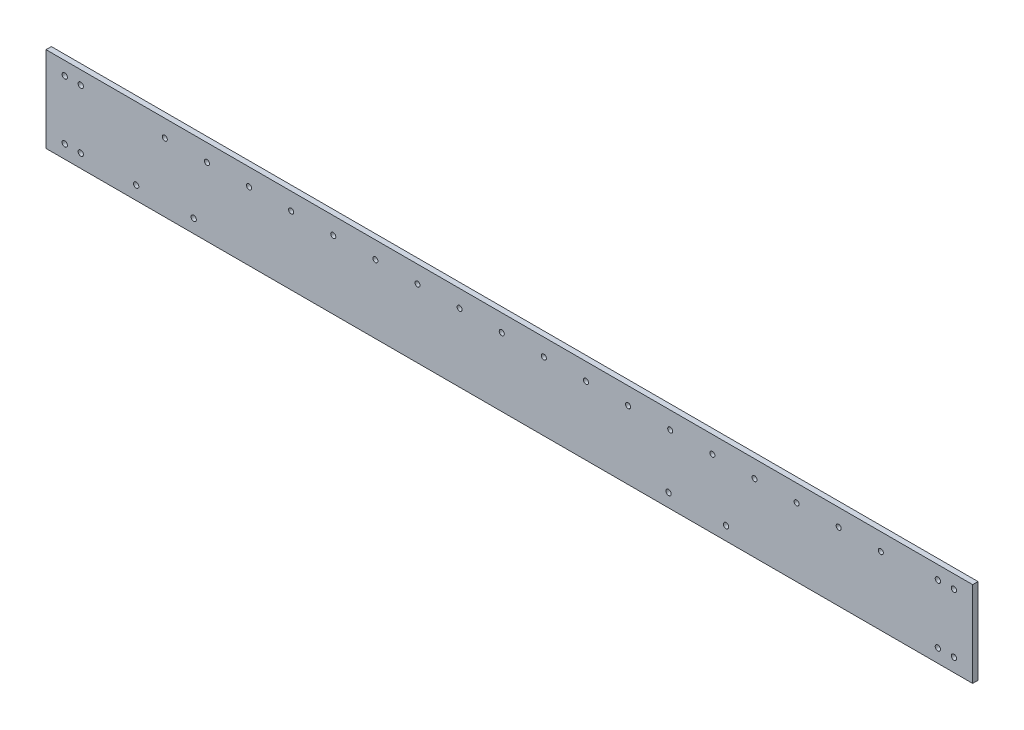
SolidWorks part; units mm, degrees
ref_plane "Front Plane" through (0, 0, 0) normal (0, 0, 1) x (1, 0, 0)
ref_plane "Top Plane" through (0, 0, 0) normal (0, 1, 0) x (1, 0, 0)
ref_plane "Right Plane" through (0, 0, 0) normal (1, 0, 0) x (0, 0, -1)
sketch "Sketch1" plane through (0, 0, 0) normal (1, 0, 0) x (0, 0, -1)
  line L0 (0, 0) -> (-3.175, 0)
  line L3 (-3.175, 0) -> (-3.175, 50.8)
  line L4 (-3.175, 50.8) -> (0, 50.8)
  line L5 (0, 50.8) -> (0, 0)
  dimension "LHeight" = 50.8
  dimension "LMaterialThickness" = 3.175
extrude "Boss-Extrude1" add sketch "Sketch1" along normal blind 550
sketch "LeftSideHoles-Sketch4" plane through (0, 0, 3.175) normal (0, 0, 1) x (1, 0, 0)
  line L0 (550, 50.8) -> (550, 0) construction
  line L1 (0, 50.8) -> (0, 0) construction
  line L2 (550, 50.8) -> (550, 0) construction
  line L3 (550, 50.8) -> (0, 50.8) construction
  line L4 (550, 0) -> (0, 0) construction
  line L5 (550, 50.8) -> (0, 50.8) construction
  line L6 (0, 50.8) -> (0, 0) construction
  circle A1 centre (11.1125, 42.8625) radius 1.5875
  circle A3 centre (529.3625, 42.8625) radius 1.5875
  circle A4 centre (20.6375, 42.8625) radius 1.5875
  circle A5 centre (538.8875, 42.8625) radius 1.5875
  circle A6 centre (11.1125, 7.9375) radius 1.5875
  circle A7 centre (20.6375, 7.9375) radius 1.5875
  circle A8 centre (529.3625, 7.9375) radius 1.5875
  circle A9 centre (538.8875, 7.9375) radius 1.5875
  circle A10 centre (495.5, 40.575) radius 1.5
  circle A11 centre (470.5, 40.575) radius 1.5
  circle A12 centre (445.5, 40.575) radius 1.5
  circle A13 centre (420.5, 40.575) radius 1.5
  circle A14 centre (395.5, 40.575) radius 1.5
  circle A15 centre (370.5, 40.575) radius 1.5
  circle A16 centre (345.5, 40.575) radius 1.5
  circle A17 centre (320.5, 40.575) radius 1.5
  circle A18 centre (295.5, 40.575) radius 1.5
  circle A19 centre (270.5, 40.575) radius 1.5
  circle A20 centre (245.5, 40.575) radius 1.5
  circle A21 centre (220.5, 40.575) radius 1.5
  circle A22 centre (195.5, 40.575) radius 1.5
  circle A23 centre (170.5, 40.575) radius 1.5
  circle A24 centre (145.5, 40.575) radius 1.5
  circle A25 centre (120.5, 40.575) radius 1.5
  circle A26 centre (95.5, 40.575) radius 1.5
  circle A27 centre (70.5, 40.575) radius 1.5
  circle A28 centre (53.5125, 7.9375) radius 1.5875
  circle A31 centre (369.5125, 7.9375) radius 1.5875
  circle A33 centre (87.6375, 7.9375) radius 1.5875
  circle A35 centre (403.6375, 7.9375) radius 1.5875
  dimension "D2" = 3.175
  dimension "D10" = 3
  dimension "D14" = 3.175
  dimension "D4" = 7.9375
  dimension "D1" = 11.1125
  dimension "D6" = 20.6375
  dimension "D3" = 11.1125
  dimension "D5" = 20.6375
  dimension "D7" = 7.9375
  dimension "D8" = 54.5
  dimension "D9" = 10.225
  dimension "D12" = 25
  dimension "D13" = 7.9375
  dimension "D15" = 53.5125
  dimension "D17" = 316
  dimension "D20" = 34.125
  dimension "D16" = 34.125
  dimension "D11" = 18
extrude "LeftSideHoles-Cut-Extrude3" cut sketch "LeftSideHoles-Sketch4" against normal through all
equation "\"RailThickness\"= .125in'Spec"
equation "\"SideRailHoleY1FromEdge\"= \"HoleOffsetFromEdge\""
equation "\"SideRailHoleX1FromSide\"= \"HoleOffsetFromSide\""
equation "\"MidSideRailLength\"= \"SideRailLength\""
equation "\"VSWidth\"= 1.25in'Spec"
equation "\"HoleOffsetFromEdge\"= \"RailThickness\" * 2.5"
equation "\"HoleOffsetFromSide\"= \"RailThickness\" * 3.5"
equation "\"SideRailHoleX2FromSide\"= \"VSWidth\" - \"HoleOffsetFromEdge\" - \"RailThickness\"'Equals 20.6375"
equation "\"FasteningHoleDiameter\"= .125in"
equation "\"D2@LeftSideHoles-Sketch4\" = \"FasteningHoleDiameter\""
equation "\"LHeight@Sketch1\"=\"MidLeftOrRightSideRailHeight\""
equation "\"LMaterialThickness@Sketch1\"=\"RailThickness\""
equation "\"D1@Boss-Extrude1\"=\"MidSideRailLength\""
equation "\"D4@LeftSideHoles-Sketch4\" = \"SideRailHoleY1FromEdge\""
equation "\"D1@LeftSideHoles-Sketch4\"=\"SideRailHoleX1FromSide\""
equation "\"D6@LeftSideHoles-Sketch4\"=\"SideRailHoleX2FromSide\" "
equation "\"D3@LeftSideHoles-Sketch4\"=\"SideRailHoleX1FromSide\" "
equation "\"D5@LeftSideHoles-Sketch4\"=\"SideRailHoleX2FromSide\" "
equation "\"D7@LeftSideHoles-Sketch4\"=\"HoleOffsetFromEdge\""
equation "\"LinearRailXMountHole\"= \"StepperWidth\" + \"LinearRailFirstHoleOffsetFromEdge\""
equation "\"D8@LeftSideHoles-Sketch4\"=\"LinearRailXMountHole\""
equation "\"D9@LeftSideHoles-Sketch4\"=\"V6.3 GantryMiddleToTopOfMidSideRail\""
equation "\"LinearRailHoleDistance\"= 25mm'Spec"
equation "\"D12@LeftSideHoles-Sketch4\"=\"LinearRailHoleDistance\""
equation "\"LinearRailFirstHoleOffsetFromEdge\"= 12.5mm'Spec"
equation "\"SideRailLength\"= 550mm"
equation "\"MidLeftOrRightSideRailHeight\"= 2.0in"
equation "\"StepperWidth\"= 42mm'Spec"
equation "\"StepperHolePadSize\"= \"StepperHoleDiameter\""
equation "\"MidRailRodStabilizerMountingHoleOffsetFromEdge\"= \"HoleOffsetFromEdge\""
equation "\"D13@LeftSideHoles-Sketch4\"=\"MidRailRodStabilizerMountingHoleOffsetFromEdge\""
equation "\"D14@LeftSideHoles-Sketch4\"=\"FasteningHoleDiameter\""
equation "\"DistanceFromBedFrontToFirstLeftStepperHole\"= \"LeadScrewNutPadSize\" + 10mm'Equals 34"
equation "\"BeltTensionerDepth\"= \"BeltTensionerBackWallThickness\" + \"BeltTensionerInnerDepth\"'Equals 23.4"
equation "\"20TGT2PulleyDiameter\"= 17.9mm'Spec"
equation "\"BeltTensionerSpaceBetweenPulleyAndWall\"= 1.5mm"
equation "\"BeltTensionerBackWallThickness\"= 4mm"
equation "\"BeltTensionerInnerDepth\"= \"20TGT2PulleyDiameter\" + \"BeltTensionerSpaceBetweenPulleyAndWall\""
equation "\"DistanceFromFrontSideToBedFront\"= \"RailThickness\" + \"BeltTensionerDepth\" + 10mm'Equals 36.575"
equation "\"DistanceFromFrontSideToFirstLeftStepperHole\"= \"DistanceFromFrontSideToBedFront\" + \"DistanceFromBedFrontToFirstLeftStepperHole\"'Equals 70.575"
equation "\"DistanceBetweenFrontToBackStepperHoles\"= \"BedLength\" - \"DistanceFromBedFrontToFirstLeftStepperHole\"'Equals 316"
equation "\"BedLength\"= \"BedInnerSquareLength\" + \"BedLWidth\" * 2 + \"BedIncreasedByLength\"'Equals 350"
equation "\"BedThirdSize\"= 70mm"
equation "\"BedInnerSquareWidth\"= \"BedThirdSize\" * 3'Equals 210"
equation "\"BedLWidth\"= \"BedThirdSize\"'Equals 70"
equation "\"BedIncreasedByLength\"= 0mm"
equation "\"BedInnerSquareLength\"= \"BedInnerSquareWidth\""
equation "\"DistanceFromFrontSideToFirstLeftRodStabilizerMountingHole\"= \"DistanceFromFrontSideToFirstLeftStepperHole\" - \"DistanceFromStepperHoleToRodStabilizerMountingHole\"'Equals 53.5125"
equation "\"D15@LeftSideHoles-Sketch4\"=\"DistanceFromFrontSideToFirstLeftRodStabilizerMountingHole\""
equation "\"D17@LeftSideHoles-Sketch4\"=\"DistanceBetweenFrontToBackStepperHoles\""
equation "\"GABMidWallHeight\"= 28mm'Must equal 28 or changes alignment"
equation "\"20TGT2PulleyWidth\"= 8.7mm'The STL of the Pulley in the diagram is a bit larger"
equation "\"GABMidShortRiserHeight\"= \"GABMidWallHeight\" / 2 - \"20TGT2PulleyWidth\"'Equals 5.3"
equation "\"GABUpperHeight\"= 6mm"
equation "\"GABLowerHeight\"= 3mm"
equation "\"GABHeight\"= \"GABLowerHeight\" + \"GABMidWallHeight\" + \"GABUpperHeight\""
equation "\"GABRiserBossOffset\"= 0.8mm'Aligns Pulleys"
equation "\"StepperShaftLength\"= 24mm'Pulley will be attached to the end"
equation "\"V6.1 FromGantryPulleyToGantryMiddle\"= \"GABHeight\" / 2 - \"GABMidShortRiserHeight\" - \"GABLowerHeight\" + \"GABRiserBossOffset\" / 2"
equation "\"V6.2 GantryMiddleToTopOfMidBackRail\"= \"StepperShaftLength\" - \"V6.1 FromGantryPulleyToGantryMiddle\""
equation "\"V6.3 GantryMiddleToTopOfMidSideRail\"= \"V6.2 GantryMiddleToTopOfMidBackRail\" - \"RailThickness\""
equation "\"LeadScrewNutMountingHoleFlangeDiameter\"= 22mm'Spec"
equation "\"LeadScrewNutPadSize\"= \"LeadScrewNutMountingHoleFlangeDiameter\" + 2mm'Equals 24"
equation "\"D20@LeftSideHoles-Sketch4\"=\"RodStabilizerLength\" - \"HoleOffsetFromEdge\" * 2"
equation "\"DistanceFromStepperHoleToRodStabilizerMountingHole\"= \"RodStabilizerLength\" / 2 - \"HoleOffsetFromEdge\"'Equals 17.0625"
equation "\"RodStabilizerLength\"= 50mm"
equation "\"D16@LeftSideHoles-Sketch4\"=\"RodStabilizerLength\" - \"HoleOffsetFromEdge\" * 2"
